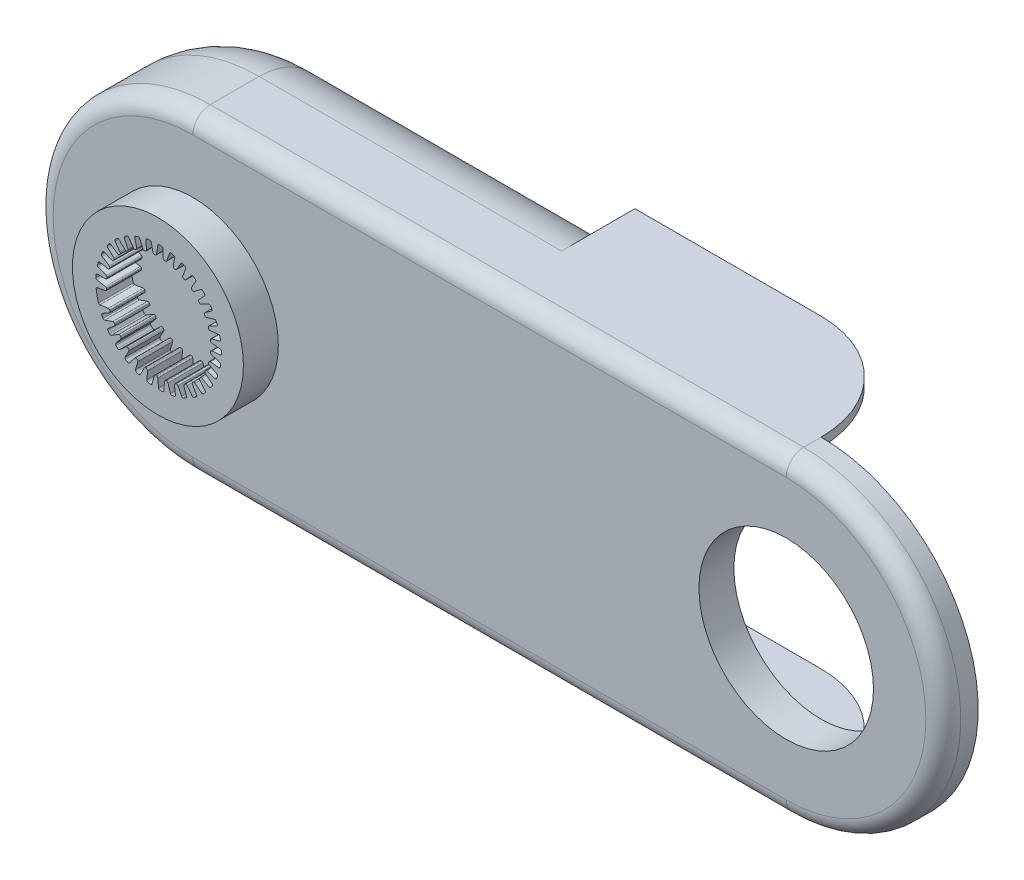
SolidWorks part; units mm, degrees
ref_plane "Front Plane" through (0, 0, 0) normal (0, 0, 1) x (1, 0, 0)
ref_plane "Top Plane" through (0, 0, 0) normal (0, 1, 0) x (1, 0, 0)
ref_plane "Right Plane" through (0, 0, 0) normal (1, 0, 0) x (0, 0, -1)
sketch "Sketch1" plane through (0, 0, 0) normal (0, 0, 1) x (1, 0, 0)
  line L0 (55, 0) -> (-55, 0) construction
  line L1 (-16.9691, -5.4979) -> (-14.565, -5.1246)
  line L2 (-14.1254, -5.3896) -> (-14.0498, -5.609)
  line L3 (-14.2318, -6.0878) -> (-16.2781, -7.2403)
  line L4 (-15.6283, -8.6059) -> (-13.3395, -7.7807)
  line L5 (-12.8575, -7.957) -> (-12.7414, -8.158)
  line L6 (-12.8287, -8.6627) -> (-14.6175, -10.1845)
  line L7 (-13.7191, -11.401) -> (-11.6298, -10.1543)
  line L8 (-11.1229, -10.2354) -> (-10.9707, -10.4105)
  line L9 (-10.96, -10.9225) -> (-12.4256, -12.7577)
  line L10 (-11.3116, -13.7804) -> (-9.4986, -12.158)
  line L11 (-8.9856, -12.1408) -> (-8.8027, -12.2837)
  line L12 (-8.6945, -12.7843) -> (-9.783, -14.8654)
  line L13 (-8.4943, -15.6568) -> (-7.0242, -13.7182)
  line L14 (-6.5239, -13.6035) -> (-6.3171, -13.7088)
  line L15 (-6.1154, -14.1796) -> (-6.7868, -16.4302)
  line L16 (-5.3708, -16.9611) -> (-4.2976, -14.7776)
  line L17 (-3.8283, -14.5696) -> (-3.6053, -14.6335)
  line L18 (-3.3174, -15.0571) -> (-3.5471, -17.3945)
  line L19 (-2.0557, -17.6455) -> (-1.4189, -15.2973)
  line L20 (-0.998, -15.0035) -> (-0.7668, -15.0238)
  line L21 (-0.4034, -15.3847) -> (-0.1828, -17.7229)
  line L22 (1.329, -17.6847) -> (1.5061, -15.2582)
  line L23 (1.8632, -14.8895) -> (2.094, -14.8652)
  line L24 (2.5196, -15.1502) -> (3.1822, -17.4034)
  line L25 (4.659, -17.0774) -> (4.3698, -14.6617)
  line L26 (4.65, -14.2316) -> (4.872, -14.1637)
  line L27 (5.3441, -14.3623) -> (6.4245, -16.4476)
  line L28 (7.8119, -15.8458) -> (7.0671, -13.5297)
  line L29 (7.2601, -13.054) -> (7.465, -12.9451)
  line L30 (7.9664, -13.0499) -> (9.4248, -14.8908)
  line L31 (10.6719, -14.0353) -> (9.4989, -11.9038)
  line L32 (9.5976, -11.4001) -> (9.7779, -11.254)
  line L33 (10.29, -11.2612) -> (12.073, -12.79)
  line L34 (13.1339, -11.7123) -> (11.5757, -9.8438)
  line L35 (11.5765, -9.3305) -> (11.7257, -9.1527)
  line L36 (12.2298, -9.0621) -> (14.2716, -10.2226)
  line L37 (15.1075, -8.9622) -> (13.2214, -7.4254)
  line L38 (13.1242, -6.9214) -> (13.2367, -6.7184)
  line L39 (13.7142, -6.5332) -> (15.94, -7.2828)
  line L40 (16.52, -5.8861) -> (14.3753, -4.7374)
  line L41 (14.1837, -4.2612) -> (14.2555, -4.0405)
  line L42 (14.6889, -3.7676) -> (17.0168, -4.0787)
  line L43 (17.3196, -2.597) -> (14.9951, -1.8786)
  line L44 (14.7162, -1.4477) -> (14.7445, -1.2173)
  line L45 (15.1179, -0.8668) -> (17.4624, -0.728)
  line L46 (17.477, 0.7843) -> (15.0581, 1.0459)
  line L47 (14.7021, 1.4157) -> (14.6859, 1.6472)
  line L48 (14.9856, 2.0626) -> (17.2605, 2.6462)
  line L49 (16.9862, 4.1334) -> (14.5619, 3.9288)
  line L50 (14.1419, 4.2238) -> (14.0818, 4.448)
  line L51 (14.2967, 4.9129) -> (16.4185, 5.9199)
  line L52 (15.8655, 7.3274) -> (13.5247, 6.6639)
  line L53 (13.0561, 6.8734) -> (12.9544, 7.082)
  line L54 (13.0766, 7.5794) -> (14.9673, 8.9727)
  line L55 (14.1559, 10.2489) -> (11.9847, 9.151)
  line L56 (11.4848, 9.2672) -> (11.3451, 9.4525)
  line L57 (11.3702, 9.9641) -> (12.9602, 11.6926)
  line L58 (11.9202, 12.7905) -> (9.9985, 11.2984)
  line L59 (9.4855, 11.3171) -> (9.3131, 11.4724)
  line L60 (9.2401, 11.9793) -> (10.4711, 13.9795)
  line L61 (9.2407, 14.8588) -> (7.6389, 13.0275)
  line L62 (7.1318, 12.9479) -> (6.9329, 13.0675)
  line L63 (6.7645, 13.5511) -> (7.5913, 15.7494)
  line L64 (6.2158, 16.3778) -> (4.9929, 14.2745)
  line L65 (4.5102, 14.0997) -> (4.2922, 14.1791)
  line L66 (4.0346, 14.6217) -> (4.4267, 16.9374)
  line L67 (2.9565, 17.2917) -> (2.1574, 14.9937)
  line L68 (1.7171, 14.73) -> (1.4878, 14.7663)
  line L69 (1.1505, 15.1517) -> (1.0936, 17.4997)
  line L70 (-0.4172, 17.567) -> (-0.7631, 15.1587)
  line L71 (-1.1451, 14.8159) -> (-1.377, 14.8078)
  line L72 (-1.7817, 15.1217) -> (-2.2855, 17.4156)
  line L73 (-3.7814, 17.1934) -> (-3.6615, 14.7634)
  line L74 (-3.971, 14.354) -> (-4.1972, 14.3018)
  line L75 (-4.6543, 14.5327) -> (-5.5866, 16.6884)
  line L76 (-7.0126, 16.1848) -> (-6.4312, 13.8224)
  line L77 (-6.6569, 13.3614) -> (-6.8689, 13.267)
  line L78 (-7.3617, 13.4065) -> (-8.6882, 15.3446)
  line L79 (-9.992, 14.5782) -> (-8.9705, 12.3701)
  line L80 (-9.1041, 11.8745) -> (-9.2942, 11.7414)
  line L81 (-9.8045, 11.7843) -> (-11.4765, 13.4337)
  line L82 (-12.61, 12.4326) -> (-11.1859, 10.46)
  line L83 (-11.2225, 9.948) -> (-11.3837, 9.7811)
  line L84 (-11.8929, 9.7258) -> (-13.8489, 11.0259)
  line L85 (-14.7706, 9.8269) -> (-12.9963, 8.1622)
  line L86 (-12.9345, 7.6527) -> (-13.0609, 7.458)
  line L87 (-13.5501, 7.3066) -> (-15.7182, 8.2096)
  line L88 (-16.3942, 6.8568) -> (-14.3349, 5.5613)
  line L89 (-14.177, 5.0729) -> (-14.264, 4.8577)
  line L90 (-14.7153, 4.6157) -> (-17.0159, 5.0884)
  line L91 (-17.4214, 3.6315) -> (-15.1526, 2.7527)
  line L92 (-14.9045, 2.3034) -> (-14.9488, 2.0756)
  line L93 (-15.3457, 1.7519) -> (-17.6942, 1.777)
  line L94 (-17.8142, 0.2694) -> (-15.4195, -0.1603)
  line L95 (-15.0901, -0.554) -> (-15.0901, -0.7861)
  line L96 (-15.418, -1.1795) -> (-17.7281, -1.6031)
  circle A0 centre (-0.372, 0) radius 24.5
  arc A1 (-18.0536, -2.0399) -> (-17.4139, -5.2165) centre (-0.1596, -0.0893) ccw
  arc A2 (-17.4139, -5.2165) -> (-16.9691, -5.4979) centre (-17.0305, -5.1026) ccw
  arc A3 (-14.1254, -5.3896) -> (-14.565, -5.1246) centre (-14.5036, -5.5198) ccw
  arc A4 (-14.2318, -6.0878) -> (-14.0498, -5.609) centre (-14.4281, -5.7393) ccw
  arc A5 (-16.2781, -7.2403) -> (-16.4437, -7.7593) centre (-16.0818, -7.5889) ccw
  arc A6 (-16.4437, -7.7593) -> (-16.1186, -8.4146) centre (-0.1596, -0.0893) ccw
  arc A7 (-16.1186, -8.4146) -> (-15.6283, -8.6059) centre (-15.764, -8.2296) ccw
  arc A8 (-12.8575, -7.957) -> (-13.3395, -7.7807) centre (-13.2039, -8.157) ccw
  arc A9 (-12.8287, -8.6627) -> (-12.7414, -8.158) centre (-13.0878, -8.358) ccw
  arc A10 (-14.6175, -10.1845) -> (-14.681, -10.7255) centre (-14.3583, -10.4892) ccw
  arc A11 (-14.681, -10.7255) -> (-14.2369, -11.3068) centre (-0.1596, -0.0893) ccw
  arc A12 (-14.2369, -11.3068) -> (-13.7191, -11.401) centre (-13.924, -11.0575) ccw
  arc A13 (-11.1229, -10.2354) -> (-11.6298, -10.1543) centre (-11.4248, -10.4978) ccw
  arc A14 (-10.96, -10.9225) -> (-10.9707, -10.4105) centre (-11.2726, -10.6729) ccw
  arc A15 (-12.4256, -12.7577) -> (-12.3847, -13.3009) centre (-12.1131, -13.0073) ccw
  arc A16 (-12.3847, -13.3009) -> (-11.8378, -13.7868) centre (-0.1596, -0.0893) ccw
  arc A17 (-11.8378, -13.7868) -> (-11.3116, -13.7804) centre (-11.5783, -13.4824) ccw
  arc A18 (-8.9856, -12.1408) -> (-9.4986, -12.158) centre (-9.2318, -12.456) ccw
  arc A19 (-8.6945, -12.7843) -> (-8.8027, -12.2837) centre (-9.049, -12.5989) ccw
  arc A20 (-9.783, -14.8654) -> (-9.6392, -15.3909) centre (-9.4286, -15.0508) ccw
  arc A21 (-9.6392, -15.3909) -> (-9.0097, -15.7634) centre (-0.1596, -0.0893) ccw
  arc A22 (-9.0097, -15.7634) -> (-8.4943, -15.6568) centre (-8.813, -15.4151) ccw
  arc A23 (-6.5239, -13.6035) -> (-7.0242, -13.7182) centre (-6.7055, -13.9599) ccw
  arc A24 (-6.1154, -14.1796) -> (-6.3171, -13.7088) centre (-6.4987, -14.0653) ccw
  arc A25 (-6.7868, -16.4302) -> (-6.5454, -16.9185) centre (-6.4035, -16.5446) ccw
  arc A26 (-6.5454, -16.9185) -> (-5.8563, -17.1641) centre (-0.1596, -0.0893) ccw
  arc A27 (-5.8563, -17.1641) -> (-5.3708, -16.9611) centre (-5.7297, -16.7847) ccw
  arc A28 (-3.8283, -14.5696) -> (-4.2976, -14.7776) centre (-3.9386, -14.9541) ccw
  arc A29 (-3.3174, -15.0571) -> (-3.6053, -14.6335) centre (-3.7155, -15.018) ccw
  arc A30 (-3.5471, -17.3945) -> (-3.2169, -17.8278) centre (-3.149, -17.4336) ccw
  arc A31 (-3.2169, -17.8278) -> (-2.4937, -17.9374) centre (-0.1596, -0.0893) ccw
  arc A32 (-2.4937, -17.9374) -> (-2.0557, -17.6455) centre (-2.4418, -17.5408) ccw
  arc A33 (-0.998, -15.0035) -> (-1.4189, -15.2973) centre (-1.0328, -15.402) ccw
  arc A34 (-0.4034, -15.3847) -> (-0.7668, -15.0238) centre (-0.8016, -15.4222) ccw
  arc A35 (-0.1828, -17.7229) -> (0.2239, -18.0853) centre (0.2154, -17.6853) ccw
  arc A36 (0.2239, -18.0853) -> (0.9548, -18.0548) centre (-0.1596, -0.0893) ccw
  arc A37 (0.9548, -18.0548) -> (1.329, -17.6847) centre (0.93, -17.6556) ccw
  arc A38 (1.8632, -14.8895) -> (1.5061, -15.2582) centre (1.905, -15.2873) ccw
  arc A39 (2.5196, -15.1502) -> (2.094, -14.8652) centre (2.1358, -15.263) ccw
  arc A40 (3.1822, -17.4034) -> (3.6506, -17.6814) centre (3.566, -17.2905) ccw
  arc A41 (3.6506, -17.6814) -> (4.3623, -17.5121) centre (-0.1596, -0.0893) ccw
  arc A42 (4.3623, -17.5121) -> (4.659, -17.0774) centre (4.2618, -17.1249) ccw
  arc A43 (4.65, -14.2316) -> (4.3698, -14.6617) centre (4.767, -14.6141) ccw
  arc A44 (5.3441, -14.3623) -> (4.872, -14.1637) centre (4.9889, -14.5463) ccw
  arc A45 (6.4245, -16.4476) -> (6.9374, -16.6312) centre (6.7797, -16.2636) ccw
  arc A46 (6.9374, -16.6312) -> (7.6036, -16.3292) centre (-0.1596, -0.0893) ccw
  arc A47 (7.6036, -16.3292) -> (7.8119, -15.8458) centre (7.4311, -15.9683) ccw
  arc A48 (7.2601, -13.054) -> (7.0671, -13.5297) centre (7.4479, -13.4072) ccw
  arc A49 (7.9664, -13.0499) -> (7.465, -12.9451) centre (7.6528, -13.2983) ccw
  arc A50 (9.4248, -14.8908) -> (9.9633, -14.9731) centre (9.7384, -14.6424) ccw
  arc A51 (9.9633, -14.9731) -> (10.5597, -14.5495) centre (-0.1596, -0.0893) ccw
  arc A52 (10.5597, -14.5495) -> (10.6719, -14.0353) centre (10.3215, -14.2282) ccw
  arc A53 (9.5976, -11.4001) -> (9.4989, -11.9038) centre (9.8493, -11.7109) ccw
  arc A54 (10.29, -11.2612) -> (9.7779, -11.254) centre (10.0297, -11.5649) ccw
  arc A55 (12.073, -12.79) -> (12.6173, -12.7681) centre (12.3334, -12.4864) ccw
  arc A56 (12.6173, -12.7681) -> (13.1219, -12.2385) centre (-0.1596, -0.0893) ccw
  arc A57 (13.1219, -12.2385) -> (13.1339, -11.7123) centre (12.8267, -11.9685) ccw
  arc A58 (11.5765, -9.3305) -> (11.5757, -9.8438) centre (11.8829, -9.5876) ccw
  arc A59 (12.2298, -9.0621) -> (11.7257, -9.1527) centre (12.0321, -9.4099) ccw
  arc A60 (14.2716, -10.2226) -> (14.8018, -10.0972) centre (14.4693, -9.8748) ccw
  arc A61 (14.8018, -10.0972) -> (15.196, -9.481) centre (-0.1596, -0.0893) ccw
  arc A62 (15.196, -9.481) -> (15.1075, -8.9622) centre (14.8548, -9.2723) ccw
  arc A63 (13.1242, -6.9214) -> (13.2214, -7.4254) centre (13.474, -7.1153) ccw
  arc A64 (13.7142, -6.5332) -> (13.2367, -6.7184) centre (13.5866, -6.9123) ccw
  arc A65 (15.94, -7.2828) -> (16.4365, -7.0586) centre (16.0677, -6.9037) ccw
  arc A66 (16.4365, -7.0586) -> (16.7059, -6.3785) centre (-0.1596, -0.0893) ccw
  arc A67 (16.7059, -6.3785) -> (16.52, -5.8861) centre (16.3311, -6.2387) ccw
  arc A68 (14.1837, -4.2612) -> (14.3753, -4.7374) centre (14.5642, -4.3848) ccw
  arc A69 (14.6889, -3.7676) -> (14.2555, -4.0405) centre (14.6359, -4.1641) ccw
  arc A70 (17.0168, -4.0787) -> (17.4613, -3.7638) centre (17.0698, -3.6822) ccw
  arc A71 (17.4613, -3.7638) -> (17.5961, -3.0448) centre (-0.1596, -0.0893) ccw
  arc A72 (17.5961, -3.0448) -> (17.3196, -2.597) centre (17.2015, -2.9792) ccw
  arc A73 (14.7162, -1.4477) -> (14.9951, -1.8786) centre (15.1133, -1.4964) ccw
  arc A74 (15.1179, -0.8668) -> (14.7445, -1.2173) centre (15.1415, -1.2661) ccw
  arc A75 (17.4624, -0.728) -> (17.8387, -0.3341) centre (17.4388, -0.3287) ccw
  arc A76 (17.8387, -0.3341) -> (17.8338, 0.3974) centre (-0.1596, -0.0893) ccw
  arc A77 (17.8338, 0.3974) -> (17.477, 0.7843) centre (17.434, 0.3866) ccw
  arc A78 (14.7021, 1.4157) -> (15.0581, 1.0459) centre (15.1011, 1.4436) ccw
  arc A79 (14.9856, 2.0626) -> (14.6859, 1.6472) centre (15.085, 1.6751) ccw
  arc A80 (17.2605, 2.6462) -> (17.5547, 3.1046) centre (17.1611, 3.0337) ccw
  arc A81 (17.5547, 3.1046) -> (17.4103, 3.8218) centre (-0.1596, -0.0893) ccw
  arc A82 (17.4103, 3.8218) -> (16.9862, 4.1334) centre (17.0199, 3.7348) ccw
  arc A83 (14.1419, 4.2238) -> (14.5619, 3.9288) centre (14.5283, 4.3274) ccw
  arc A84 (14.2967, 4.9129) -> (14.0818, 4.448) centre (14.4682, 4.5515) ccw
  arc A85 (16.4185, 5.9199) -> (16.6198, 6.426) centre (16.247, 6.2812) ccw
  arc A86 (16.6198, 6.426) -> (16.3413, 7.1024) centre (-0.1596, -0.0893) ccw
  arc A87 (16.3413, 7.1024) -> (15.8655, 7.3274) centre (15.9746, 6.9426) ccw
  arc A88 (13.0561, 6.8734) -> (13.5247, 6.6639) centre (13.4156, 7.0488) ccw
  arc A89 (13.0766, 7.5794) -> (12.9544, 7.082) centre (13.3139, 7.2574) ccw
  arc A90 (14.9673, 8.9727) -> (15.0684, 9.508) centre (14.73, 9.2947) ccw
  arc A91 (15.0684, 9.508) -> (14.6658, 10.1188) centre (-0.1596, -0.0893) ccw
  arc A92 (14.6658, 10.1188) -> (14.1559, 10.2489) centre (14.3364, 9.8919) ccw
  arc A93 (11.4848, 9.2672) -> (11.9847, 9.151) centre (11.8042, 9.5079) ccw
  arc A94 (11.3702, 9.9641) -> (11.3451, 9.4525) centre (11.6646, 9.6932) ccw
  arc A95 (12.9602, 11.6926) -> (12.9573, 12.2373) centre (12.6658, 11.9634) ccw
  arc A96 (12.9573, 12.2373) -> (12.4456, 12.7601) centre (-0.1596, -0.0893) ccw
  arc A97 (12.4456, 12.7601) -> (11.9202, 12.7905) centre (12.1655, 12.4745) ccw
  arc A98 (9.4855, 11.3171) -> (9.9985, 11.2984) centre (9.7532, 11.6144) ccw
  arc A99 (9.2401, 11.9793) -> (9.3131, 11.4724) centre (9.5807, 11.7697) ccw
  arc A100 (10.4711, 13.9795) -> (10.3643, 14.5136) centre (10.1304, 14.1891) ccw
  arc A101 (10.3643, 14.5136) -> (9.7623, 14.9292) centre (-0.1596, -0.0893) ccw
  arc A102 (9.7623, 14.9292) -> (9.2407, 14.8588) centre (9.5418, 14.5954) ccw
  arc A103 (7.1318, 12.9479) -> (7.6389, 13.0275) centre (7.3379, 13.2908) ccw
  arc A104 (6.7645, 13.5511) -> (6.9329, 13.0675) centre (7.1389, 13.4103) ccw
  arc A105 (7.5913, 15.7494) -> (7.3846, 16.2534) centre (7.2169, 15.8902) ccw
  arc A106 (7.3846, 16.2534) -> (6.7143, 16.5464) centre (-0.1596, -0.0893) ccw
  arc A107 (6.7143, 16.5464) -> (6.2158, 16.3778) centre (6.5616, 16.1768) ccw
  arc A108 (4.5102, 14.0997) -> (4.9929, 14.2745) centre (4.6471, 14.4756) ccw
  arc A109 (4.0346, 14.6217) -> (4.2922, 14.1791) centre (4.429, 14.5549) ccw
  arc A110 (4.4267, 16.9374) -> (4.1276, 17.3926) centre (4.0323, 17.0042) ccw
  arc A111 (4.1276, 17.3926) -> (3.4138, 17.5524) centre (-0.1596, -0.0893) ccw
  arc A112 (3.4138, 17.5524) -> (2.9565, 17.2917) centre (3.3343, 17.1604) ccw
  arc A113 (1.7171, 14.73) -> (2.1574, 14.9937) centre (1.7796, 15.1251) ccw
  arc A114 (1.1505, 15.1517) -> (1.4878, 14.7663) centre (1.5504, 15.1614) ccw
  arc A115 (1.0936, 17.4997) -> (0.7131, 17.8895) centre (0.6937, 17.49) ccw
  arc A116 (0.7131, 17.8895) -> (-0.0181, 17.9101) centre (-0.1596, -0.0893) ccw
  arc A117 (-0.0181, 17.9101) -> (-0.4172, 17.567) centre (-0.0212, 17.5101) ccw
  arc A118 (-1.1451, 14.8159) -> (-0.7631, 15.1587) centre (-1.1591, 15.2156) ccw
  arc A119 (-1.7817, 15.1217) -> (-1.377, 14.8078) centre (-1.391, 15.2075) ccw
  arc A120 (-2.2855, 17.4156) -> (-2.7334, 17.7257) centre (-2.6762, 17.3298) ccw
  arc A121 (-2.7334, 17.7257) -> (-3.4552, 17.6064) centre (-0.1596, -0.0893) ccw
  arc A122 (-3.4552, 17.6064) -> (-3.7814, 17.1934) centre (-3.3819, 17.2132) ccw
  arc A123 (-3.971, 14.354) -> (-3.6615, 14.7634) centre (-4.061, 14.7437) ccw
  arc A124 (-4.6543, 14.5327) -> (-4.1972, 14.3018) centre (-4.2871, 14.6915) ccw
  arc A125 (-5.5866, 16.6884) -> (-6.0854, 16.9073) centre (-5.9537, 16.5296) ccw
  arc A126 (-6.0854, 16.9073) -> (-6.7711, 16.6525) centre (-0.1596, -0.0893) ccw
  arc A127 (-6.7711, 16.6525) -> (-7.0126, 16.1848) centre (-6.6242, 16.2804) ccw
  arc A128 (-6.6569, 13.3614) -> (-6.4312, 13.8224) centre (-6.8196, 13.7268) ccw
  arc A129 (-7.3617, 13.4065) -> (-6.8689, 13.267) centre (-7.0316, 13.6324) ccw
  arc A130 (-8.6882, 15.3446) -> (-9.2196, 15.4643) centre (-9.0183, 15.1187) ccw
  arc A131 (-9.2196, 15.4643) -> (-9.8441, 15.0833) centre (-0.1596, -0.0893) ccw
  arc A132 (-9.8441, 15.0833) -> (-9.992, 14.5782) centre (-9.6289, 14.7462) ccw
  arc A133 (-9.1041, 11.8745) -> (-8.9705, 12.3701) centre (-9.3335, 12.2021) ccw
  arc A134 (-9.8045, 11.7843) -> (-9.2942, 11.7414) centre (-9.5236, 12.069) ccw
  arc A135 (-11.4765, 13.4337) -> (-12.021, 13.4498) centre (-11.7574, 13.1489) ccw
  arc A136 (-12.021, 13.4498) -> (-12.5613, 12.9567) centre (-0.1596, -0.0893) ccw
  arc A137 (-12.5613, 12.9567) -> (-12.61, 12.4326) centre (-12.2857, 12.6668) ccw
  arc A138 (-11.2225, 9.948) -> (-11.1859, 10.46) centre (-11.5103, 10.2259) ccw
  arc A139 (-11.8929, 9.7258) -> (-11.3837, 9.7811) centre (-11.6715, 10.0589) ccw
  arc A140 (-13.8489, 11.0259) -> (-14.3864, 10.9378) centre (-14.0703, 10.6928) ccw
  arc A141 (-14.3864, 10.9378) -> (-14.8227, 10.3506) centre (-0.1596, -0.0893) ccw
  arc A142 (-14.8227, 10.3506) -> (-14.7706, 9.8269) centre (-14.4969, 10.1186) ccw
  arc A143 (-12.9345, 7.6527) -> (-12.9963, 8.1622) centre (-13.27, 7.8705) ccw
  arc A144 (-13.5501, 7.3066) -> (-13.0609, 7.458) centre (-13.3963, 7.6759) ccw
  arc A145 (-15.7182, 8.2096) -> (-16.2291, 8.0206) centre (-15.872, 7.8404) ccw
  arc A146 (-16.2291, 8.0206) -> (-16.5454, 7.361) centre (-0.1596, -0.0893) ccw
  arc A147 (-16.5454, 7.361) -> (-16.3942, 6.8568) centre (-16.1812, 7.1954) ccw
  arc A148 (-14.177, 5.0729) -> (-14.3349, 5.5613) centre (-14.5479, 5.2227) ccw
  arc A149 (-14.7153, 4.6157) -> (-14.264, 4.8577) centre (-14.6348, 5.0075) ccw
  arc A150 (-17.0159, 5.0884) -> (-17.4813, 4.8054) centre (-17.0964, 4.6966) ccw
  arc A151 (-17.4813, 4.8054) -> (-17.6659, 4.0975) centre (-0.1596, -0.0893) ccw
  arc A152 (-17.6659, 4.0975) -> (-17.4214, 3.6315) centre (-17.2769, 4.0045) ccw
  arc A153 (-14.9045, 2.3034) -> (-15.1526, 2.7527) centre (-15.2971, 2.3797) ccw
  arc A154 (-15.3457, 1.7519) -> (-14.9488, 2.0756) centre (-15.3414, 2.1519) ccw
  arc A155 (-17.6942, 1.777) -> (-18.097, 1.4103) centre (-17.6984, 1.377) ccw
  arc A156 (-18.097, 1.4103) -> (-18.1432, 0.6803) centre (-0.1596, -0.0893) ccw
  arc A157 (-18.1432, 0.6803) -> (-17.8142, 0.2694) centre (-17.7435, 0.6632) ccw
  arc A158 (-15.0901, -0.554) -> (-15.4195, -0.1603) centre (-15.4901, -0.554) ccw
  arc A159 (-15.418, -1.1795) -> (-15.0901, -0.7861) centre (-15.4901, -0.7861) ccw
  arc A160 (-17.7281, -1.6031) -> (-18.0536, -2.0399) centre (-17.656, -1.9965) ccw
  dimension "D1" = 49
extrude "Boss-Extrude1" add sketch "Sketch1" along normal blind 10
sketch "Sketch6" plane through (0, 0, 0) normal (0, 0, 1) x (1, 0, 0)
  line L0 (-0.372, 0) -> (169.628, 0) construction
  line L1 (-0.372, 45) -> (169.628, 45)
  line L2 (169.628, -45) -> (-0.372, -45)
  arc A1 (169.628, -45) -> (169.628, 45) centre (169.628, 0) ccw
  arc A2 (-0.372, 45) -> (-0.372, -45) centre (-0.372, 0) ccw
  dimension "D1" = 170
  dimension "D2" = 90
extrude "Boss-Extrude3" add sketch "Sketch6" against normal blind 40
sketch "Sketch7" plane through (0, 0, -40) normal (0, 0, -1) x (-1, 0, 0)
  line L6 (-174.2492, 0) -> (0, 0) construction
  line L7 (-169.628, 42.5) -> (-91.4373, 42.5)
  line L8 (-257.0612, 42.5) -> (-257.0612, -42.5)
  line L9 (-169.628, -42.5) -> (-91.4373, -42.5)
  line L10 (-91.4373, 42.5) -> (-91.4373, -42.5)
  line L11 (-257.0612, 42.5) -> (-91.4373, -42.5) construction
  line L12 (-257.0612, -42.5) -> (-91.4373, 42.5) construction
  line L13 (-169.628, 45) -> (-169.628, 42.5)
  line L14 (-169.628, 45) -> (-257.0612, 45)
  line L15 (-257.0612, 45) -> (-257.0612, 42.5)
  line L16 (-169.628, -45) -> (-169.628, -42.5)
  line L17 (-169.628, -45) -> (-257.0612, -45)
  line L18 (-257.0612, -45) -> (-257.0612, -42.5)
  point P0 (-174.2492, 0)
  dimension "D1" = 85
extrude "Cut-Extrude3" cut sketch "Sketch7" against normal blind 30
fillet "Fillet12" radius 5 4 edges at (-45.372, 0, 0) (84.628, -45, 0) (84.628, 45, 0) (214.628, 0, 0)
fillet "Fillet14" radius 30 2 edges at (169.628, -43.75, -40) (169.628, 43.75, -40)
sketch "Sketch8" plane through (0, 0, -40) normal (0, 0, -1) x (-1, 0, 0)
  line L0 (-139.628, 45) -> (0.372, 45) construction
  line L1 (-86.2755, 45) -> (62.0003, 45)
  line L2 (-86.2755, 45) -> (-86.2755, -45)
  line L3 (-86.2755, -45) -> (62.0003, -45)
  line L4 (62.0003, 45) -> (62.0003, -45)
  line L5 (0.372, -45) -> (-139.628, -45) construction
extrude "Cut-Extrude4" cut sketch "Sketch8" against normal blind 1
fillet "Fillet16" radius 20 3 edges at (42.9518, -45, -39) (-45.372, 0, -39) (42.9518, 45, -39)
sketch "Sketch9" plane through (0, 0, -10) normal (0, 0, -1) x (-1, 0, 0)
  circle A0 centre (-169.628, 0) radius 25
extrude "Cut-Extrude5" cut sketch "Sketch9" against normal through all
scale "Scale1" scale about centroid uniform scaling yes scale factor 0.3
